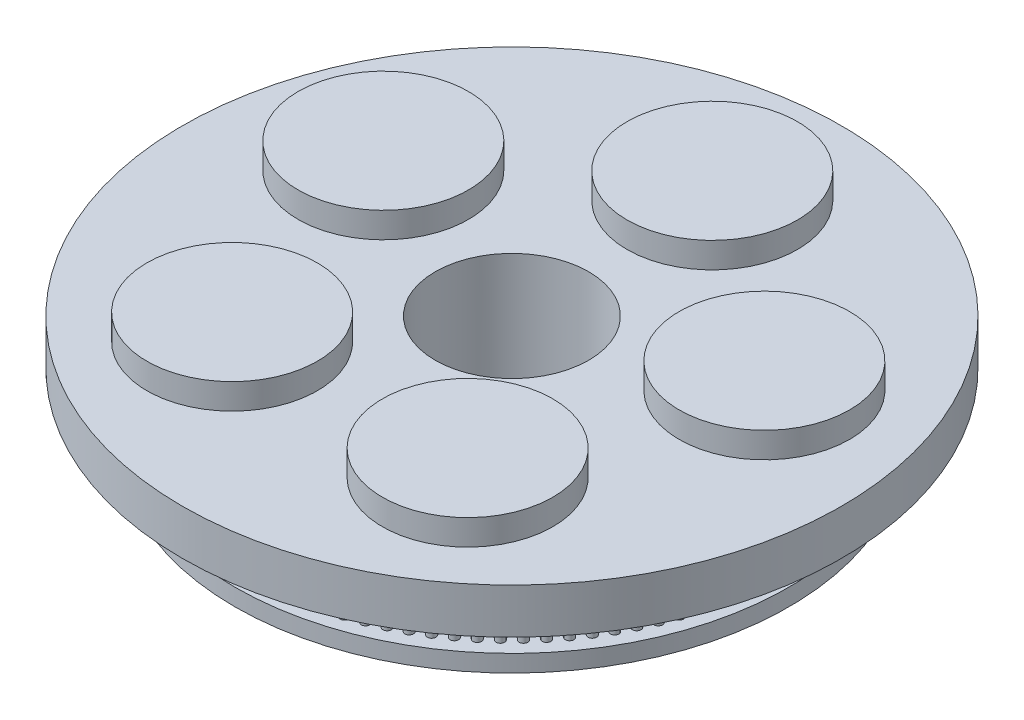
SolidWorks part; units mm, degrees
ref_plane "前基準面" through (0, 0, 0) normal (0, 0, 1) x (1, 0, 0)
ref_plane "上基準面" through (0, 0, 0) normal (0, 1, 0) x (1, 0, 0)
ref_plane "右基準面" through (0, 0, 0) normal (1, 0, 0) x (0, 0, -1)
sketch "草圖1" plane through (0, 0, 0) normal (0, 1, 0) x (1, 0, 0)
  circle A0 centre (0, 0) radius 38.66
  circle A1 centre (0, 0) radius 9
  dimension "D1" = 77.32
  dimension "D2" = 18
extrude "填料-伸長1" add sketch "草圖1" along normal blind 5.3
sketch "草圖3" plane through (0, 0, 0) normal (0, 0, 1) x (1, 0, 0)
  line L0 (0, 0) -> (0, 14.4931) construction
sketch "草圖2" plane through (0, 5.3, 0) normal (0, 1, 0) x (1, 0, 0)
  circle A0 centre (0, 23.5) radius 10
  dimension "D1" = 20
  dimension "D2" = 23.5
extrude "填料-伸長2" add sketch "草圖2" along normal blind 3
pattern_circular "環狀複製排列1" count 5 over 360 about axis through (0, 0, 0) along (0, 1, 0) of "填料-伸長2" reverse direction yes
sketch "草圖4" plane through (0, 0, 0) normal (0, -1, 0) x (1, 0, 0)
  line L0 (0, 0) -> (0, 38.66) construction
  line L1 (-0.5, 30.56) -> (-0.5, 29.9958) construction
  line L2 (-0.5, 30.56) -> (-0.5, 30.41)
  line L3 (0.5, 30.56) -> (0.5, 30.41)
  line L4 (1.4199, 30.5311) -> (1.4104, 30.3814)
  line L5 (2.4179, 30.4683) -> (2.4085, 30.3186)
  line L6 (3.3341, 30.3817) -> (3.3153, 30.2329)
  line L7 (4.3262, 30.2564) -> (4.3074, 30.1075)
  line L8 (5.2352, 30.1124) -> (5.2071, 29.965)
  line L9 (6.2175, 29.925) -> (6.1894, 29.7777)
  line L10 (7.1157, 29.7242) -> (7.0784, 29.579)
  line L11 (8.0843, 29.4756) -> (8.047, 29.3303)
  line L12 (8.968, 29.2188) -> (8.9217, 29.0761)
  line L13 (9.9191, 28.9098) -> (9.8727, 28.7671)
  line L14 (10.785, 28.598) -> (10.7298, 28.4586)
  line L15 (11.7148, 28.2299) -> (11.6596, 28.0904)
  line L16 (12.5594, 27.8644) -> (12.4955, 27.7287)
  line L17 (13.4642, 27.4386) -> (13.4004, 27.3029)
  line L18 (14.2842, 27.0208) -> (14.212, 26.8894)
  line L19 (15.1605, 26.5391) -> (15.0883, 26.4076)
  line L20 (15.9527, 26.0706) -> (15.8723, 25.9439)
  line L21 (16.797, 25.5347) -> (16.7167, 25.4081)
  line L22 (17.5582, 25.0175) -> (17.47, 24.8961)
  line L23 (18.3672, 24.4297) -> (18.2791, 24.3083)
  line L24 (19.0944, 23.8656) -> (18.9988, 23.75)
  line L25 (19.8649, 23.2282) -> (19.7693, 23.1126)
  line L26 (20.5553, 22.6196) -> (20.4526, 22.5102)
  line L27 (21.2842, 21.935) -> (21.1816, 21.8257)
  line L28 (21.935, 21.2842) -> (21.8257, 21.1816)
  line L29 (22.6196, 20.5553) -> (22.5102, 20.4526)
  line L30 (23.2282, 19.8649) -> (23.1126, 19.7693)
  line L31 (23.8656, 19.0944) -> (23.75, 18.9988)
  line L32 (24.4297, 18.3672) -> (24.3083, 18.2791)
  line L33 (25.0175, 17.5582) -> (24.8961, 17.47)
  line L34 (25.5347, 16.797) -> (25.4081, 16.7167)
  line L35 (26.0706, 15.9527) -> (25.9439, 15.8723)
  line L36 (26.5391, 15.1605) -> (26.4076, 15.0883)
  line L37 (27.0208, 14.2842) -> (26.8894, 14.212)
  line L38 (27.4386, 13.4642) -> (27.3029, 13.4004)
  line L39 (27.8644, 12.5594) -> (27.7287, 12.4955)
  line L40 (28.2299, 11.7148) -> (28.0904, 11.6596)
  line L41 (28.598, 10.785) -> (28.4586, 10.7298)
  line L42 (28.9098, 9.9191) -> (28.7671, 9.8727)
  line L43 (29.2188, 8.968) -> (29.0761, 8.9217)
  line L44 (29.4756, 8.0843) -> (29.3303, 8.047)
  line L45 (29.7242, 7.1157) -> (29.579, 7.0784)
  line L46 (29.925, 6.2175) -> (29.7777, 6.1894)
  line L47 (30.1124, 5.2352) -> (29.965, 5.2071)
  line L48 (30.2564, 4.3262) -> (30.1075, 4.3074)
  line L49 (30.3817, 3.3341) -> (30.2329, 3.3153)
  line L50 (30.4683, 2.4179) -> (30.3186, 2.4085)
  line L51 (30.5311, 1.4199) -> (30.3814, 1.4104)
  line L52 (30.56, 0.5) -> (30.41, 0.5)
  line L53 (30.56, -0.5) -> (30.41, -0.5)
  line L54 (30.5311, -1.4199) -> (30.3814, -1.4104)
  line L55 (30.4683, -2.4179) -> (30.3186, -2.4085)
  line L56 (30.3817, -3.3341) -> (30.2329, -3.3153)
  line L57 (30.2564, -4.3262) -> (30.1075, -4.3074)
  line L58 (30.1124, -5.2352) -> (29.965, -5.2071)
  line L59 (29.925, -6.2175) -> (29.7777, -6.1894)
  line L60 (29.7242, -7.1157) -> (29.579, -7.0784)
  line L61 (29.4756, -8.0843) -> (29.3303, -8.047)
  line L62 (29.2188, -8.968) -> (29.0761, -8.9217)
  line L63 (28.9098, -9.9191) -> (28.7671, -9.8727)
  line L64 (28.598, -10.785) -> (28.4586, -10.7298)
  line L65 (28.2299, -11.7148) -> (28.0904, -11.6596)
  line L66 (27.8644, -12.5594) -> (27.7287, -12.4955)
  line L67 (27.4386, -13.4642) -> (27.3029, -13.4004)
  line L68 (27.0208, -14.2842) -> (26.8894, -14.212)
  line L69 (26.5391, -15.1605) -> (26.4076, -15.0883)
  line L70 (26.0706, -15.9527) -> (25.9439, -15.8723)
  line L71 (25.5347, -16.797) -> (25.4081, -16.7167)
  line L72 (25.0175, -17.5582) -> (24.8961, -17.47)
  line L73 (24.4297, -18.3672) -> (24.3083, -18.2791)
  line L74 (23.8656, -19.0944) -> (23.75, -18.9988)
  line L75 (23.2282, -19.8649) -> (23.1126, -19.7693)
  line L76 (22.6196, -20.5553) -> (22.5102, -20.4526)
  line L77 (21.935, -21.2842) -> (21.8257, -21.1816)
  line L78 (21.2842, -21.935) -> (21.1816, -21.8257)
  line L79 (20.5553, -22.6196) -> (20.4526, -22.5102)
  line L80 (19.8649, -23.2282) -> (19.7693, -23.1126)
  line L81 (19.0944, -23.8656) -> (18.9988, -23.75)
  line L82 (18.3672, -24.4297) -> (18.2791, -24.3083)
  line L83 (17.5582, -25.0175) -> (17.47, -24.8961)
  line L84 (16.797, -25.5347) -> (16.7167, -25.4081)
  line L85 (15.9527, -26.0706) -> (15.8723, -25.9439)
  line L86 (15.1605, -26.5391) -> (15.0883, -26.4076)
  line L87 (14.2842, -27.0208) -> (14.212, -26.8894)
  line L88 (13.4642, -27.4386) -> (13.4004, -27.3029)
  line L89 (12.5594, -27.8644) -> (12.4955, -27.7287)
  line L90 (11.7148, -28.2299) -> (11.6596, -28.0904)
  line L91 (10.785, -28.598) -> (10.7298, -28.4586)
  line L92 (9.9191, -28.9098) -> (9.8727, -28.7671)
  line L93 (8.968, -29.2188) -> (8.9217, -29.0761)
  line L94 (8.0843, -29.4756) -> (8.047, -29.3303)
  line L95 (7.1157, -29.7242) -> (7.0784, -29.579)
  line L96 (6.2175, -29.925) -> (6.1894, -29.7777)
  line L97 (5.2352, -30.1124) -> (5.2071, -29.965)
  line L98 (4.3262, -30.2564) -> (4.3074, -30.1075)
  line L99 (3.3341, -30.3817) -> (3.3153, -30.2329)
  line L100 (2.4179, -30.4683) -> (2.4085, -30.3186)
  line L101 (1.4199, -30.5311) -> (1.4104, -30.3814)
  line L102 (0.5, -30.56) -> (0.5, -30.41)
  line L103 (-0.5, -30.56) -> (-0.5, -30.41)
  line L104 (-1.4199, -30.5311) -> (-1.4104, -30.3814)
  line L105 (-2.4179, -30.4683) -> (-2.4085, -30.3186)
  line L106 (-3.3341, -30.3817) -> (-3.3153, -30.2329)
  line L107 (-4.3262, -30.2564) -> (-4.3074, -30.1075)
  line L108 (-5.2352, -30.1124) -> (-5.2071, -29.965)
  line L109 (-6.2175, -29.925) -> (-6.1894, -29.7777)
  line L110 (-7.1157, -29.7242) -> (-7.0784, -29.579)
  line L111 (-8.0843, -29.4756) -> (-8.047, -29.3303)
  line L112 (-8.968, -29.2188) -> (-8.9217, -29.0761)
  line L113 (-9.9191, -28.9098) -> (-9.8727, -28.7671)
  line L114 (-10.785, -28.598) -> (-10.7298, -28.4586)
  line L115 (-11.7148, -28.2299) -> (-11.6596, -28.0904)
  line L116 (-12.5594, -27.8644) -> (-12.4955, -27.7287)
  line L117 (-13.4642, -27.4386) -> (-13.4004, -27.3029)
  line L118 (-14.2842, -27.0208) -> (-14.212, -26.8894)
  line L119 (-15.1605, -26.5391) -> (-15.0883, -26.4076)
  line L120 (-15.9527, -26.0706) -> (-15.8723, -25.9439)
  line L121 (-16.797, -25.5347) -> (-16.7167, -25.4081)
  line L122 (-17.5582, -25.0175) -> (-17.47, -24.8961)
  line L123 (-18.3672, -24.4297) -> (-18.2791, -24.3083)
  line L124 (-19.0944, -23.8656) -> (-18.9988, -23.75)
  line L125 (-19.8649, -23.2282) -> (-19.7693, -23.1126)
  line L126 (-20.5553, -22.6196) -> (-20.4526, -22.5102)
  line L127 (-21.2842, -21.935) -> (-21.1816, -21.8257)
  line L128 (-21.935, -21.2842) -> (-21.8257, -21.1816)
  line L129 (-22.6196, -20.5553) -> (-22.5102, -20.4526)
  line L130 (-23.2282, -19.8649) -> (-23.1126, -19.7693)
  line L131 (-23.8656, -19.0944) -> (-23.75, -18.9988)
  line L132 (-24.4297, -18.3672) -> (-24.3083, -18.2791)
  line L133 (-25.0175, -17.5582) -> (-24.8961, -17.47)
  line L134 (-25.5347, -16.797) -> (-25.4081, -16.7167)
  line L135 (-26.0706, -15.9527) -> (-25.9439, -15.8723)
  line L136 (-26.5391, -15.1605) -> (-26.4076, -15.0883)
  line L137 (-27.0208, -14.2842) -> (-26.8894, -14.212)
  line L138 (-27.4386, -13.4642) -> (-27.3029, -13.4004)
  line L139 (-27.8644, -12.5594) -> (-27.7287, -12.4955)
  line L140 (-28.2299, -11.7148) -> (-28.0904, -11.6596)
  line L141 (-28.598, -10.785) -> (-28.4586, -10.7298)
  line L142 (-28.9098, -9.9191) -> (-28.7671, -9.8727)
  line L143 (-29.2188, -8.968) -> (-29.0761, -8.9217)
  line L144 (-29.4756, -8.0843) -> (-29.3303, -8.047)
  line L145 (-29.7242, -7.1157) -> (-29.579, -7.0784)
  line L146 (-29.925, -6.2175) -> (-29.7777, -6.1894)
  line L147 (-30.1124, -5.2352) -> (-29.965, -5.2071)
  line L148 (-30.2564, -4.3262) -> (-30.1075, -4.3074)
  line L149 (-30.3817, -3.3341) -> (-30.2329, -3.3153)
  line L150 (-30.4683, -2.4179) -> (-30.3186, -2.4085)
  line L151 (-30.5311, -1.4199) -> (-30.3814, -1.4104)
  line L152 (-30.56, -0.5) -> (-30.41, -0.5)
  line L153 (-30.56, 0.5) -> (-30.41, 0.5)
  line L154 (-30.5311, 1.4199) -> (-30.3814, 1.4104)
  line L155 (-30.4683, 2.4179) -> (-30.3186, 2.4085)
  line L156 (-30.3817, 3.3341) -> (-30.2329, 3.3153)
  line L157 (-30.2564, 4.3262) -> (-30.1075, 4.3074)
  line L158 (-30.1124, 5.2352) -> (-29.965, 5.2071)
  line L159 (-29.925, 6.2175) -> (-29.7777, 6.1894)
  line L160 (-29.7242, 7.1157) -> (-29.579, 7.0784)
  line L161 (-29.4756, 8.0843) -> (-29.3303, 8.047)
  line L162 (-29.2188, 8.968) -> (-29.0761, 8.9217)
  line L163 (-28.9098, 9.9191) -> (-28.7671, 9.8727)
  line L164 (-28.598, 10.785) -> (-28.4586, 10.7298)
  line L165 (-28.2299, 11.7148) -> (-28.0904, 11.6596)
  line L166 (-27.8644, 12.5594) -> (-27.7287, 12.4955)
  line L167 (-27.4386, 13.4642) -> (-27.3029, 13.4004)
  line L168 (-27.0208, 14.2842) -> (-26.8894, 14.212)
  line L169 (-26.5391, 15.1605) -> (-26.4076, 15.0883)
  line L170 (-26.0706, 15.9527) -> (-25.9439, 15.8723)
  line L171 (-25.5347, 16.797) -> (-25.4081, 16.7167)
  line L172 (-25.0175, 17.5582) -> (-24.8961, 17.47)
  line L173 (-24.4297, 18.3672) -> (-24.3083, 18.2791)
  line L174 (-23.8656, 19.0944) -> (-23.75, 18.9988)
  line L175 (-23.2282, 19.8649) -> (-23.1126, 19.7693)
  line L176 (-22.6196, 20.5553) -> (-22.5102, 20.4526)
  line L177 (-21.935, 21.2842) -> (-21.8257, 21.1816)
  line L178 (-21.2842, 21.935) -> (-21.1816, 21.8257)
  line L179 (-20.5553, 22.6196) -> (-20.4526, 22.5102)
  line L180 (-19.8649, 23.2282) -> (-19.7693, 23.1126)
  line L181 (-19.0944, 23.8656) -> (-18.9988, 23.75)
  line L182 (-18.3672, 24.4297) -> (-18.2791, 24.3083)
  line L183 (-17.5582, 25.0175) -> (-17.47, 24.8961)
  line L184 (-16.797, 25.5347) -> (-16.7167, 25.4081)
  line L185 (-15.9527, 26.0706) -> (-15.8723, 25.9439)
  line L186 (-15.1605, 26.5391) -> (-15.0883, 26.4076)
  line L187 (-14.2842, 27.0208) -> (-14.212, 26.8894)
  line L188 (-13.4642, 27.4386) -> (-13.4004, 27.3029)
  line L189 (-12.5594, 27.8644) -> (-12.4955, 27.7287)
  line L190 (-11.7148, 28.2299) -> (-11.6596, 28.0904)
  line L191 (-10.785, 28.598) -> (-10.7298, 28.4586)
  line L192 (-9.9191, 28.9098) -> (-9.8727, 28.7671)
  line L193 (-8.968, 29.2188) -> (-8.9217, 29.0761)
  line L194 (-8.0843, 29.4756) -> (-8.047, 29.3303)
  line L195 (-7.1157, 29.7242) -> (-7.0784, 29.579)
  line L196 (-6.2175, 29.925) -> (-6.1894, 29.7777)
  line L197 (-5.2352, 30.1124) -> (-5.2071, 29.965)
  line L198 (-4.3262, 30.2564) -> (-4.3074, 30.1075)
  line L199 (-3.3341, 30.3817) -> (-3.3153, 30.2329)
  line L200 (-2.4179, 30.4683) -> (-2.4085, 30.3186)
  line L201 (-1.4199, 30.5311) -> (-1.4104, 30.3814)
  circle A0 centre (0, 0) radius 30.56 construction
  circle A1 centre (0, 0) radius 30
  circle A2 centre (0, 0) radius 38.66 construction
  arc A3 (0.5, 30.5559) -> (-0.5, 30.56) centre (0, 30.56) ccw
  arc A4 (-0.5, 30.41) -> (-0.9112, 29.9862) centre (-0.924, 30.41) cw
  arc A5 (2.4176, 30.4642) -> (1.4199, 30.5311) centre (1.9189, 30.4997) ccw
  arc A6 (1.4104, 30.3814) -> (0.9735, 29.9842) centre (0.9872, 30.408) cw
  arc A7 (0.5, 30.41) -> (0.9112, 29.9862) centre (0.924, 30.41) ccw
  arc A8 (2.4085, 30.3186) -> (2.7922, 29.8698) centre (2.8317, 30.292) ccw
  arc A9 (4.3257, 30.2523) -> (3.3341, 30.3817) centre (3.8302, 30.319) ccw
  arc A10 (3.3153, 30.2329) -> (2.8543, 29.8639) centre (2.8946, 30.286) cw
  arc A11 (4.3074, 30.1075) -> (4.6622, 29.6355) centre (4.7281, 30.0544) ccw
  arc A12 (6.2167, 29.921) -> (5.2352, 30.1124) centre (5.7264, 30.0187) ccw
  arc A13 (5.2071, 29.965) -> (4.7238, 29.6258) centre (4.7906, 30.0445) cw
  arc A14 (6.1894, 29.7777) -> (6.5139, 29.2843) centre (6.6059, 29.6982) ccw
  arc A15 (8.0832, 29.4716) -> (7.1157, 29.7242) centre (7.6, 29.5999) ccw
  arc A16 (7.0784, 29.579) -> (6.5747, 29.2707) centre (6.6677, 29.6844) cw
  arc A17 (8.047, 29.3303) -> (8.3398, 28.8175) centre (8.4577, 29.2248) ccw
  arc A18 (9.9178, 28.9059) -> (8.968, 29.2188) centre (9.4436, 29.0643) ccw
  arc A19 (8.9217, 29.0761) -> (8.3997, 28.8001) centre (8.5184, 29.2072) cw
  arc A20 (9.8727, 28.7671) -> (10.1328, 28.237) centre (10.276, 28.6361) ccw
  arc A21 (11.7133, 28.2261) -> (10.785, 28.598) centre (11.2499, 28.414) ccw
  arc A22 (10.7298, 28.4586) -> (10.1915, 28.2158) centre (10.3355, 28.6147) cw
  arc A23 (11.6596, 28.0904) -> (11.8858, 27.545) centre (12.0538, 27.9343) ccw
  arc A24 (13.4625, 27.4349) -> (12.5594, 27.8644) centre (13.0118, 27.6515) ccw
  arc A25 (12.4955, 27.7287) -> (11.943, 27.5202) centre (12.1119, 27.9092) cw
  arc A26 (13.4004, 27.3029) -> (13.5919, 26.7443) centre (13.784, 27.1224) ccw
  arc A27 (15.1586, 26.5355) -> (14.2842, 27.0208) centre (14.7224, 26.7799) ccw
  arc A28 (14.212, 26.8894) -> (13.6475, 26.716) centre (13.8404, 27.0936) cw
  arc A29 (15.0883, 26.4076) -> (15.2444, 25.8381) centre (15.4599, 26.2033) ccw
  arc A30 (16.7948, 25.5313) -> (15.9527, 26.0706) centre (16.3749, 25.8027) ccw
  arc A31 (15.8723, 25.9439) -> (15.2981, 25.8064) centre (15.5143, 26.1711) cw
  arc A32 (16.7167, 25.4081) -> (16.8367, 24.8299) centre (17.0747, 25.1809) ccw
  arc A33 (18.3648, 24.4264) -> (17.5582, 25.0175) centre (17.9627, 24.7236) ccw
  arc A34 (17.47, 24.8961) -> (16.8883, 24.7949) centre (17.127, 25.1453) cw
  arc A35 (18.2791, 24.3083) -> (18.3626, 23.7237) centre (18.6221, 24.0591) ccw
  arc A36 (19.8623, 23.225) -> (19.0944, 23.8656) centre (19.4797, 23.5469) ccw
  arc A37 (18.9988, 23.75) -> (18.4118, 23.6855) centre (18.6721, 24.0203) cw
  arc A38 (19.7693, 23.1126) -> (19.816, 22.5239) centre (20.096, 22.8423) ccw
  arc A39 (21.2814, 21.932) -> (20.5553, 22.6196) centre (20.9198, 22.2773) ccw
  arc A40 (20.4526, 22.5102) -> (19.8627, 22.4827) centre (20.1435, 22.8005) cw
  arc A41 (21.1816, 21.8257) -> (21.1911, 21.2352) centre (21.4907, 21.5354) ccw
  arc A42 (22.6166, 20.5525) -> (21.935, 21.2842) centre (22.2773, 20.9198) ccw
  arc A43 (21.8257, 21.1816) -> (21.2352, 21.1911) centre (21.5354, 21.4907) cw
  arc A44 (22.5102, 20.4526) -> (22.4827, 19.8627) centre (22.8005, 20.1435) ccw
  arc A45 (23.8624, 19.0918) -> (23.2282, 19.8649) centre (23.5469, 19.4797) ccw
  arc A46 (23.1126, 19.7693) -> (22.5239, 19.816) centre (22.8423, 20.096) cw
  arc A47 (23.75, 18.9988) -> (23.6855, 18.4118) centre (24.0203, 18.6721) ccw
  arc A48 (25.0141, 17.5558) -> (24.4297, 18.3672) centre (24.7236, 17.9627) ccw
  arc A49 (24.3083, 18.2791) -> (23.7237, 18.3626) centre (24.0591, 18.6221) cw
  arc A50 (24.8961, 17.47) -> (24.7949, 16.8883) centre (25.1453, 17.127) ccw
  arc A51 (26.0671, 15.9505) -> (25.5347, 16.797) centre (25.8027, 16.3749) ccw
  arc A52 (25.4081, 16.7167) -> (24.8299, 16.8367) centre (25.1809, 17.0747) cw
  arc A53 (25.9439, 15.8723) -> (25.8064, 15.2981) centre (26.1711, 15.5143) ccw
  arc A54 (27.0172, 14.2823) -> (26.5391, 15.1605) centre (26.7799, 14.7224) ccw
  arc A55 (26.4076, 15.0883) -> (25.8381, 15.2444) centre (26.2033, 15.4599) cw
  arc A56 (26.8894, 14.212) -> (26.716, 13.6475) centre (27.0936, 13.8404) ccw
  arc A57 (27.8607, 12.5577) -> (27.4386, 13.4642) centre (27.6515, 13.0118) ccw
  arc A58 (27.3029, 13.4004) -> (26.7443, 13.5919) centre (27.1224, 13.784) cw
  arc A59 (27.7287, 12.4955) -> (27.5202, 11.943) centre (27.9092, 12.1119) ccw
  arc A60 (28.5942, 10.7835) -> (28.2299, 11.7148) centre (28.414, 11.2499) ccw
  arc A61 (28.0904, 11.6596) -> (27.545, 11.8858) centre (27.9343, 12.0538) cw
  arc A62 (28.4586, 10.7298) -> (28.2158, 10.1915) centre (28.6147, 10.3355) ccw
  arc A63 (29.2149, 8.9668) -> (28.9098, 9.9191) centre (29.0643, 9.4436) ccw
  arc A64 (28.7671, 9.8727) -> (28.237, 10.1328) centre (28.6361, 10.276) cw
  arc A65 (29.0761, 8.9217) -> (28.8001, 8.3997) centre (29.2072, 8.5184) ccw
  arc A66 (29.7203, 7.1147) -> (29.4756, 8.0843) centre (29.5999, 7.6) ccw
  arc A67 (29.3303, 8.047) -> (28.8175, 8.3398) centre (29.2248, 8.4577) cw
  arc A68 (29.579, 7.0784) -> (29.2707, 6.5747) centre (29.6844, 6.6677) ccw
  arc A69 (30.1084, 5.2345) -> (29.925, 6.2175) centre (30.0187, 5.7264) ccw
  arc A70 (29.7777, 6.1894) -> (29.2843, 6.5139) centre (29.6982, 6.6059) cw
  arc A71 (29.965, 5.2071) -> (29.6258, 4.7238) centre (30.0445, 4.7906) ccw
  arc A72 (30.3776, 3.3336) -> (30.2564, 4.3262) centre (30.319, 3.8302) ccw
  arc A73 (30.1075, 4.3074) -> (29.6355, 4.6622) centre (30.0544, 4.7281) cw
  arc A74 (30.2329, 3.3153) -> (29.8639, 2.8543) centre (30.286, 2.8946) ccw
  arc A75 (30.527, 1.4196) -> (30.4683, 2.4179) centre (30.4997, 1.9189) ccw
  arc A76 (30.3186, 2.4085) -> (29.8698, 2.7922) centre (30.292, 2.8317) cw
  arc A77 (30.3814, 1.4104) -> (29.9842, 0.9735) centre (30.408, 0.9872) ccw
  arc A78 (30.5559, -0.5) -> (30.56, 0.5) centre (30.56, 0) ccw
  arc A79 (30.41, 0.5) -> (29.9862, 0.9112) centre (30.41, 0.924) cw
  arc A80 (30.41, -0.5) -> (29.9862, -0.9112) centre (30.41, -0.924) ccw
  arc A81 (30.4642, -2.4176) -> (30.5311, -1.4199) centre (30.4997, -1.9189) ccw
  arc A82 (30.3814, -1.4104) -> (29.9842, -0.9735) centre (30.408, -0.9872) cw
  arc A83 (30.3186, -2.4085) -> (29.8698, -2.7922) centre (30.292, -2.8317) ccw
  arc A84 (30.2523, -4.3257) -> (30.3817, -3.3341) centre (30.319, -3.8302) ccw
  arc A85 (30.2329, -3.3153) -> (29.8639, -2.8543) centre (30.286, -2.8946) cw
  arc A86 (30.1075, -4.3074) -> (29.6355, -4.6622) centre (30.0544, -4.7281) ccw
  arc A87 (29.921, -6.2167) -> (30.1124, -5.2352) centre (30.0187, -5.7264) ccw
  arc A88 (29.965, -5.2071) -> (29.6258, -4.7238) centre (30.0445, -4.7906) cw
  arc A89 (29.7777, -6.1894) -> (29.2843, -6.5139) centre (29.6982, -6.6059) ccw
  arc A90 (29.4716, -8.0832) -> (29.7242, -7.1157) centre (29.5999, -7.6) ccw
  arc A91 (29.579, -7.0784) -> (29.2707, -6.5747) centre (29.6844, -6.6677) cw
  arc A92 (29.3303, -8.047) -> (28.8175, -8.3398) centre (29.2248, -8.4577) ccw
  arc A93 (28.9059, -9.9178) -> (29.2188, -8.968) centre (29.0643, -9.4436) ccw
  arc A94 (29.0761, -8.9217) -> (28.8001, -8.3997) centre (29.2072, -8.5184) cw
  arc A95 (28.7671, -9.8727) -> (28.237, -10.1328) centre (28.6361, -10.276) ccw
  arc A96 (28.2261, -11.7133) -> (28.598, -10.785) centre (28.414, -11.2499) ccw
  arc A97 (28.4586, -10.7298) -> (28.2158, -10.1915) centre (28.6147, -10.3355) cw
  arc A98 (28.0904, -11.6596) -> (27.545, -11.8858) centre (27.9343, -12.0538) ccw
  arc A99 (27.4349, -13.4625) -> (27.8644, -12.5594) centre (27.6515, -13.0118) ccw
  arc A100 (27.7287, -12.4955) -> (27.5202, -11.943) centre (27.9092, -12.1119) cw
  arc A101 (27.3029, -13.4004) -> (26.7443, -13.5919) centre (27.1224, -13.784) ccw
  arc A102 (26.5355, -15.1586) -> (27.0208, -14.2842) centre (26.7799, -14.7224) ccw
  arc A103 (26.8894, -14.212) -> (26.716, -13.6475) centre (27.0936, -13.8404) cw
  arc A104 (26.4076, -15.0883) -> (25.8381, -15.2444) centre (26.2033, -15.4599) ccw
  arc A105 (25.5313, -16.7948) -> (26.0706, -15.9527) centre (25.8027, -16.3749) ccw
  arc A106 (25.9439, -15.8723) -> (25.8064, -15.2981) centre (26.1711, -15.5143) cw
  arc A107 (25.4081, -16.7167) -> (24.8299, -16.8367) centre (25.1809, -17.0747) ccw
  arc A108 (24.4264, -18.3648) -> (25.0175, -17.5582) centre (24.7236, -17.9627) ccw
  arc A109 (24.8961, -17.47) -> (24.7949, -16.8883) centre (25.1453, -17.127) cw
  arc A110 (24.3083, -18.2791) -> (23.7237, -18.3626) centre (24.0591, -18.6221) ccw
  arc A111 (23.225, -19.8623) -> (23.8656, -19.0944) centre (23.5469, -19.4797) ccw
  arc A112 (23.75, -18.9988) -> (23.6855, -18.4118) centre (24.0203, -18.6721) cw
  arc A113 (23.1126, -19.7693) -> (22.5239, -19.816) centre (22.8423, -20.096) ccw
  arc A114 (21.932, -21.2814) -> (22.6196, -20.5553) centre (22.2773, -20.9198) ccw
  arc A115 (22.5102, -20.4526) -> (22.4827, -19.8627) centre (22.8005, -20.1435) cw
  arc A116 (21.8257, -21.1816) -> (21.2352, -21.1911) centre (21.5354, -21.4907) ccw
  arc A117 (20.5525, -22.6166) -> (21.2842, -21.935) centre (20.9198, -22.2773) ccw
  arc A118 (21.1816, -21.8257) -> (21.1911, -21.2352) centre (21.4907, -21.5354) cw
  arc A119 (20.4526, -22.5102) -> (19.8627, -22.4827) centre (20.1435, -22.8005) ccw
  arc A120 (19.0918, -23.8624) -> (19.8649, -23.2282) centre (19.4797, -23.5469) ccw
  arc A121 (19.7693, -23.1126) -> (19.816, -22.5239) centre (20.096, -22.8423) cw
  arc A122 (18.9988, -23.75) -> (18.4118, -23.6855) centre (18.6721, -24.0203) ccw
  arc A123 (17.5558, -25.0141) -> (18.3672, -24.4297) centre (17.9627, -24.7236) ccw
  arc A124 (18.2791, -24.3083) -> (18.3626, -23.7237) centre (18.6221, -24.0591) cw
  arc A125 (17.47, -24.8961) -> (16.8883, -24.7949) centre (17.127, -25.1453) ccw
  arc A126 (15.9505, -26.0671) -> (16.797, -25.5347) centre (16.3749, -25.8027) ccw
  arc A127 (16.7167, -25.4081) -> (16.8367, -24.8299) centre (17.0747, -25.1809) cw
  arc A128 (15.8723, -25.9439) -> (15.2981, -25.8064) centre (15.5143, -26.1711) ccw
  arc A129 (14.2823, -27.0172) -> (15.1605, -26.5391) centre (14.7224, -26.7799) ccw
  arc A130 (15.0883, -26.4076) -> (15.2444, -25.8381) centre (15.4599, -26.2033) cw
  arc A131 (14.212, -26.8894) -> (13.6475, -26.716) centre (13.8404, -27.0936) ccw
  arc A132 (12.5577, -27.8607) -> (13.4642, -27.4386) centre (13.0118, -27.6515) ccw
  arc A133 (13.4004, -27.3029) -> (13.5919, -26.7443) centre (13.784, -27.1224) cw
  arc A134 (12.4955, -27.7287) -> (11.943, -27.5202) centre (12.1119, -27.9092) ccw
  arc A135 (10.7835, -28.5942) -> (11.7148, -28.2299) centre (11.2499, -28.414) ccw
  arc A136 (11.6596, -28.0904) -> (11.8858, -27.545) centre (12.0538, -27.9343) cw
  arc A137 (10.7298, -28.4586) -> (10.1915, -28.2158) centre (10.3355, -28.6147) ccw
  arc A138 (8.9668, -29.2149) -> (9.9191, -28.9098) centre (9.4436, -29.0643) ccw
  arc A139 (9.8727, -28.7671) -> (10.1328, -28.237) centre (10.276, -28.6361) cw
  arc A140 (8.9217, -29.0761) -> (8.3997, -28.8001) centre (8.5184, -29.2072) ccw
  arc A141 (7.1147, -29.7203) -> (8.0843, -29.4756) centre (7.6, -29.5999) ccw
  arc A142 (8.047, -29.3303) -> (8.3398, -28.8175) centre (8.4577, -29.2248) cw
  arc A143 (7.0784, -29.579) -> (6.5747, -29.2707) centre (6.6677, -29.6844) ccw
  arc A144 (5.2345, -30.1084) -> (6.2175, -29.925) centre (5.7264, -30.0187) ccw
  arc A145 (6.1894, -29.7777) -> (6.5139, -29.2843) centre (6.6059, -29.6982) cw
  arc A146 (5.2071, -29.965) -> (4.7238, -29.6258) centre (4.7906, -30.0445) ccw
  arc A147 (3.3336, -30.3776) -> (4.3262, -30.2564) centre (3.8302, -30.319) ccw
  arc A148 (4.3074, -30.1075) -> (4.6622, -29.6355) centre (4.7281, -30.0544) cw
  arc A149 (3.3153, -30.2329) -> (2.8543, -29.8639) centre (2.8946, -30.286) ccw
  arc A150 (1.4196, -30.527) -> (2.4179, -30.4683) centre (1.9189, -30.4997) ccw
  arc A151 (2.4085, -30.3186) -> (2.7922, -29.8698) centre (2.8317, -30.292) cw
  arc A152 (1.4104, -30.3814) -> (0.9735, -29.9842) centre (0.9872, -30.408) ccw
  arc A153 (-0.5, -30.5559) -> (0.5, -30.56) centre (0, -30.56) ccw
  arc A154 (0.5, -30.41) -> (0.9112, -29.9862) centre (0.924, -30.41) cw
  arc A155 (-0.5, -30.41) -> (-0.9112, -29.9862) centre (-0.924, -30.41) ccw
  arc A156 (-2.4176, -30.4642) -> (-1.4199, -30.5311) centre (-1.9189, -30.4997) ccw
  arc A157 (-1.4104, -30.3814) -> (-0.9735, -29.9842) centre (-0.9872, -30.408) cw
  arc A158 (-2.4085, -30.3186) -> (-2.7922, -29.8698) centre (-2.8317, -30.292) ccw
  arc A159 (-4.3257, -30.2523) -> (-3.3341, -30.3817) centre (-3.8302, -30.319) ccw
  arc A160 (-3.3153, -30.2329) -> (-2.8543, -29.8639) centre (-2.8946, -30.286) cw
  arc A161 (-4.3074, -30.1075) -> (-4.6622, -29.6355) centre (-4.7281, -30.0544) ccw
  arc A162 (-6.2167, -29.921) -> (-5.2352, -30.1124) centre (-5.7264, -30.0187) ccw
  arc A163 (-5.2071, -29.965) -> (-4.7238, -29.6258) centre (-4.7906, -30.0445) cw
  arc A164 (-6.1894, -29.7777) -> (-6.5139, -29.2843) centre (-6.6059, -29.6982) ccw
  arc A165 (-8.0832, -29.4716) -> (-7.1157, -29.7242) centre (-7.6, -29.5999) ccw
  arc A166 (-7.0784, -29.579) -> (-6.5747, -29.2707) centre (-6.6677, -29.6844) cw
  arc A167 (-8.047, -29.3303) -> (-8.3398, -28.8175) centre (-8.4577, -29.2248) ccw
  arc A168 (-9.9178, -28.9059) -> (-8.968, -29.2188) centre (-9.4436, -29.0643) ccw
  arc A169 (-8.9217, -29.0761) -> (-8.3997, -28.8001) centre (-8.5184, -29.2072) cw
  arc A170 (-9.8727, -28.7671) -> (-10.1328, -28.237) centre (-10.276, -28.6361) ccw
  arc A171 (-11.7133, -28.2261) -> (-10.785, -28.598) centre (-11.2499, -28.414) ccw
  arc A172 (-10.7298, -28.4586) -> (-10.1915, -28.2158) centre (-10.3355, -28.6147) cw
  arc A173 (-11.6596, -28.0904) -> (-11.8858, -27.545) centre (-12.0538, -27.9343) ccw
  arc A174 (-13.4625, -27.4349) -> (-12.5594, -27.8644) centre (-13.0118, -27.6515) ccw
  arc A175 (-12.4955, -27.7287) -> (-11.943, -27.5202) centre (-12.1119, -27.9092) cw
  arc A176 (-13.4004, -27.3029) -> (-13.5919, -26.7443) centre (-13.784, -27.1224) ccw
  arc A177 (-15.1586, -26.5355) -> (-14.2842, -27.0208) centre (-14.7224, -26.7799) ccw
  arc A178 (-14.212, -26.8894) -> (-13.6475, -26.716) centre (-13.8404, -27.0936) cw
  arc A179 (-15.0883, -26.4076) -> (-15.2444, -25.8381) centre (-15.4599, -26.2033) ccw
  arc A180 (-16.7948, -25.5313) -> (-15.9527, -26.0706) centre (-16.3749, -25.8027) ccw
  arc A181 (-15.8723, -25.9439) -> (-15.2981, -25.8064) centre (-15.5143, -26.1711) cw
  arc A182 (-16.7167, -25.4081) -> (-16.8367, -24.8299) centre (-17.0747, -25.1809) ccw
  arc A183 (-18.3648, -24.4264) -> (-17.5582, -25.0175) centre (-17.9627, -24.7236) ccw
  arc A184 (-17.47, -24.8961) -> (-16.8883, -24.7949) centre (-17.127, -25.1453) cw
  arc A185 (-18.2791, -24.3083) -> (-18.3626, -23.7237) centre (-18.6221, -24.0591) ccw
  arc A186 (-19.8623, -23.225) -> (-19.0944, -23.8656) centre (-19.4797, -23.5469) ccw
  arc A187 (-18.9988, -23.75) -> (-18.4118, -23.6855) centre (-18.6721, -24.0203) cw
  arc A188 (-19.7693, -23.1126) -> (-19.816, -22.5239) centre (-20.096, -22.8423) ccw
  arc A189 (-21.2814, -21.932) -> (-20.5553, -22.6196) centre (-20.9198, -22.2773) ccw
  arc A190 (-20.4526, -22.5102) -> (-19.8627, -22.4827) centre (-20.1435, -22.8005) cw
  arc A191 (-21.1816, -21.8257) -> (-21.1911, -21.2352) centre (-21.4907, -21.5354) ccw
  arc A192 (-22.6166, -20.5525) -> (-21.935, -21.2842) centre (-22.2773, -20.9198) ccw
  arc A193 (-21.8257, -21.1816) -> (-21.2352, -21.1911) centre (-21.5354, -21.4907) cw
  arc A194 (-22.5102, -20.4526) -> (-22.4827, -19.8627) centre (-22.8005, -20.1435) ccw
  arc A195 (-23.8624, -19.0918) -> (-23.2282, -19.8649) centre (-23.5469, -19.4797) ccw
  arc A196 (-23.1126, -19.7693) -> (-22.5239, -19.816) centre (-22.8423, -20.096) cw
  arc A197 (-23.75, -18.9988) -> (-23.6855, -18.4118) centre (-24.0203, -18.6721) ccw
  arc A198 (-25.0141, -17.5558) -> (-24.4297, -18.3672) centre (-24.7236, -17.9627) ccw
  arc A199 (-24.3083, -18.2791) -> (-23.7237, -18.3626) centre (-24.0591, -18.6221) cw
  arc A200 (-24.8961, -17.47) -> (-24.7949, -16.8883) centre (-25.1453, -17.127) ccw
  arc A201 (-26.0671, -15.9505) -> (-25.5347, -16.797) centre (-25.8027, -16.3749) ccw
  arc A202 (-25.4081, -16.7167) -> (-24.8299, -16.8367) centre (-25.1809, -17.0747) cw
  arc A203 (-25.9439, -15.8723) -> (-25.8064, -15.2981) centre (-26.1711, -15.5143) ccw
  arc A204 (-27.0172, -14.2823) -> (-26.5391, -15.1605) centre (-26.7799, -14.7224) ccw
  arc A205 (-26.4076, -15.0883) -> (-25.8381, -15.2444) centre (-26.2033, -15.4599) cw
  arc A206 (-26.8894, -14.212) -> (-26.716, -13.6475) centre (-27.0936, -13.8404) ccw
  arc A207 (-27.8607, -12.5577) -> (-27.4386, -13.4642) centre (-27.6515, -13.0118) ccw
  arc A208 (-27.3029, -13.4004) -> (-26.7443, -13.5919) centre (-27.1224, -13.784) cw
  arc A209 (-27.7287, -12.4955) -> (-27.5202, -11.943) centre (-27.9092, -12.1119) ccw
  arc A210 (-28.5942, -10.7835) -> (-28.2299, -11.7148) centre (-28.414, -11.2499) ccw
  arc A211 (-28.0904, -11.6596) -> (-27.545, -11.8858) centre (-27.9343, -12.0538) cw
  arc A212 (-28.4586, -10.7298) -> (-28.2158, -10.1915) centre (-28.6147, -10.3355) ccw
  arc A213 (-29.2149, -8.9668) -> (-28.9098, -9.9191) centre (-29.0643, -9.4436) ccw
  arc A214 (-28.7671, -9.8727) -> (-28.237, -10.1328) centre (-28.6361, -10.276) cw
  arc A215 (-29.0761, -8.9217) -> (-28.8001, -8.3997) centre (-29.2072, -8.5184) ccw
  arc A216 (-29.7203, -7.1147) -> (-29.4756, -8.0843) centre (-29.5999, -7.6) ccw
  arc A217 (-29.3303, -8.047) -> (-28.8175, -8.3398) centre (-29.2248, -8.4577) cw
  arc A218 (-29.579, -7.0784) -> (-29.2707, -6.5747) centre (-29.6844, -6.6677) ccw
  arc A219 (-30.1084, -5.2345) -> (-29.925, -6.2175) centre (-30.0187, -5.7264) ccw
  arc A220 (-29.7777, -6.1894) -> (-29.2843, -6.5139) centre (-29.6982, -6.6059) cw
  arc A221 (-29.965, -5.2071) -> (-29.6258, -4.7238) centre (-30.0445, -4.7906) ccw
  arc A222 (-30.3776, -3.3336) -> (-30.2564, -4.3262) centre (-30.319, -3.8302) ccw
  arc A223 (-30.1075, -4.3074) -> (-29.6355, -4.6622) centre (-30.0544, -4.7281) cw
  arc A224 (-30.2329, -3.3153) -> (-29.8639, -2.8543) centre (-30.286, -2.8946) ccw
  arc A225 (-30.527, -1.4196) -> (-30.4683, -2.4179) centre (-30.4997, -1.9189) ccw
  arc A226 (-30.3186, -2.4085) -> (-29.8698, -2.7922) centre (-30.292, -2.8317) cw
  arc A227 (-30.3814, -1.4104) -> (-29.9842, -0.9735) centre (-30.408, -0.9872) ccw
  arc A228 (-30.5559, 0.5) -> (-30.56, -0.5) centre (-30.56, 0) ccw
  arc A229 (-30.41, -0.5) -> (-29.9862, -0.9112) centre (-30.41, -0.924) cw
  arc A230 (-30.41, 0.5) -> (-29.9862, 0.9112) centre (-30.41, 0.924) ccw
  arc A231 (-30.4642, 2.4176) -> (-30.5311, 1.4199) centre (-30.4997, 1.9189) ccw
  arc A232 (-30.3814, 1.4104) -> (-29.9842, 0.9735) centre (-30.408, 0.9872) cw
  arc A233 (-30.3186, 2.4085) -> (-29.8698, 2.7922) centre (-30.292, 2.8317) ccw
  arc A234 (-30.2523, 4.3257) -> (-30.3817, 3.3341) centre (-30.319, 3.8302) ccw
  arc A235 (-30.2329, 3.3153) -> (-29.8639, 2.8543) centre (-30.286, 2.8946) cw
  arc A236 (-30.1075, 4.3074) -> (-29.6355, 4.6622) centre (-30.0544, 4.7281) ccw
  arc A237 (-29.921, 6.2167) -> (-30.1124, 5.2352) centre (-30.0187, 5.7264) ccw
  arc A238 (-29.965, 5.2071) -> (-29.6258, 4.7238) centre (-30.0445, 4.7906) cw
  arc A239 (-29.7777, 6.1894) -> (-29.2843, 6.5139) centre (-29.6982, 6.6059) ccw
  arc A240 (-29.4716, 8.0832) -> (-29.7242, 7.1157) centre (-29.5999, 7.6) ccw
  arc A241 (-29.579, 7.0784) -> (-29.2707, 6.5747) centre (-29.6844, 6.6677) cw
  arc A242 (-29.3303, 8.047) -> (-28.8175, 8.3398) centre (-29.2248, 8.4577) ccw
  arc A243 (-28.9059, 9.9178) -> (-29.2188, 8.968) centre (-29.0643, 9.4436) ccw
  arc A244 (-29.0761, 8.9217) -> (-28.8001, 8.3997) centre (-29.2072, 8.5184) cw
  arc A245 (-28.7671, 9.8727) -> (-28.237, 10.1328) centre (-28.6361, 10.276) ccw
  arc A246 (-28.2261, 11.7133) -> (-28.598, 10.785) centre (-28.414, 11.2499) ccw
  arc A247 (-28.4586, 10.7298) -> (-28.2158, 10.1915) centre (-28.6147, 10.3355) cw
  arc A248 (-28.0904, 11.6596) -> (-27.545, 11.8858) centre (-27.9343, 12.0538) ccw
  arc A249 (-27.4349, 13.4625) -> (-27.8644, 12.5594) centre (-27.6515, 13.0118) ccw
  arc A250 (-27.7287, 12.4955) -> (-27.5202, 11.943) centre (-27.9092, 12.1119) cw
  arc A251 (-27.3029, 13.4004) -> (-26.7443, 13.5919) centre (-27.1224, 13.784) ccw
  arc A252 (-26.5355, 15.1586) -> (-27.0208, 14.2842) centre (-26.7799, 14.7224) ccw
  arc A253 (-26.8894, 14.212) -> (-26.716, 13.6475) centre (-27.0936, 13.8404) cw
  arc A254 (-26.4076, 15.0883) -> (-25.8381, 15.2444) centre (-26.2033, 15.4599) ccw
  arc A255 (-25.5313, 16.7948) -> (-26.0706, 15.9527) centre (-25.8027, 16.3749) ccw
  arc A256 (-25.9439, 15.8723) -> (-25.8064, 15.2981) centre (-26.1711, 15.5143) cw
  arc A257 (-25.4081, 16.7167) -> (-24.8299, 16.8367) centre (-25.1809, 17.0747) ccw
  arc A258 (-24.4264, 18.3648) -> (-25.0175, 17.5582) centre (-24.7236, 17.9627) ccw
  arc A259 (-24.8961, 17.47) -> (-24.7949, 16.8883) centre (-25.1453, 17.127) cw
  arc A260 (-24.3083, 18.2791) -> (-23.7237, 18.3626) centre (-24.0591, 18.6221) ccw
  arc A261 (-23.225, 19.8623) -> (-23.8656, 19.0944) centre (-23.5469, 19.4797) ccw
  arc A262 (-23.75, 18.9988) -> (-23.6855, 18.4118) centre (-24.0203, 18.6721) cw
  arc A263 (-23.1126, 19.7693) -> (-22.5239, 19.816) centre (-22.8423, 20.096) ccw
  arc A264 (-21.932, 21.2814) -> (-22.6196, 20.5553) centre (-22.2773, 20.9198) ccw
  arc A265 (-22.5102, 20.4526) -> (-22.4827, 19.8627) centre (-22.8005, 20.1435) cw
  arc A266 (-21.8257, 21.1816) -> (-21.2352, 21.1911) centre (-21.5354, 21.4907) ccw
  arc A267 (-20.5525, 22.6166) -> (-21.2842, 21.935) centre (-20.9198, 22.2773) ccw
  arc A268 (-21.1816, 21.8257) -> (-21.1911, 21.2352) centre (-21.4907, 21.5354) cw
  arc A269 (-20.4526, 22.5102) -> (-19.8627, 22.4827) centre (-20.1435, 22.8005) ccw
  arc A270 (-19.0918, 23.8624) -> (-19.8649, 23.2282) centre (-19.4797, 23.5469) ccw
  arc A271 (-19.7693, 23.1126) -> (-19.816, 22.5239) centre (-20.096, 22.8423) cw
  arc A272 (-18.9988, 23.75) -> (-18.4118, 23.6855) centre (-18.6721, 24.0203) ccw
  arc A273 (-17.5558, 25.0141) -> (-18.3672, 24.4297) centre (-17.9627, 24.7236) ccw
  arc A274 (-18.2791, 24.3083) -> (-18.3626, 23.7237) centre (-18.6221, 24.0591) cw
  arc A275 (-17.47, 24.8961) -> (-16.8883, 24.7949) centre (-17.127, 25.1453) ccw
  arc A276 (-15.9505, 26.0671) -> (-16.797, 25.5347) centre (-16.3749, 25.8027) ccw
  arc A277 (-16.7167, 25.4081) -> (-16.8367, 24.8299) centre (-17.0747, 25.1809) cw
  arc A278 (-15.8723, 25.9439) -> (-15.2981, 25.8064) centre (-15.5143, 26.1711) ccw
  arc A279 (-14.2823, 27.0172) -> (-15.1605, 26.5391) centre (-14.7224, 26.7799) ccw
  arc A280 (-15.0883, 26.4076) -> (-15.2444, 25.8381) centre (-15.4599, 26.2033) cw
  arc A281 (-14.212, 26.8894) -> (-13.6475, 26.716) centre (-13.8404, 27.0936) ccw
  arc A282 (-12.5577, 27.8607) -> (-13.4642, 27.4386) centre (-13.0118, 27.6515) ccw
  arc A283 (-13.4004, 27.3029) -> (-13.5919, 26.7443) centre (-13.784, 27.1224) cw
  arc A284 (-12.4955, 27.7287) -> (-11.943, 27.5202) centre (-12.1119, 27.9092) ccw
  arc A285 (-10.7835, 28.5942) -> (-11.7148, 28.2299) centre (-11.2499, 28.414) ccw
  arc A286 (-11.6596, 28.0904) -> (-11.8858, 27.545) centre (-12.0538, 27.9343) cw
  arc A287 (-10.7298, 28.4586) -> (-10.1915, 28.2158) centre (-10.3355, 28.6147) ccw
  arc A288 (-8.9668, 29.2149) -> (-9.9191, 28.9098) centre (-9.4436, 29.0643) ccw
  arc A289 (-9.8727, 28.7671) -> (-10.1328, 28.237) centre (-10.276, 28.6361) cw
  arc A290 (-8.9217, 29.0761) -> (-8.3997, 28.8001) centre (-8.5184, 29.2072) ccw
  arc A291 (-7.1147, 29.7203) -> (-8.0843, 29.4756) centre (-7.6, 29.5999) ccw
  arc A292 (-8.047, 29.3303) -> (-8.3398, 28.8175) centre (-8.4577, 29.2248) cw
  arc A293 (-7.0784, 29.579) -> (-6.5747, 29.2707) centre (-6.6677, 29.6844) ccw
  arc A294 (-5.2345, 30.1084) -> (-6.2175, 29.925) centre (-5.7264, 30.0187) ccw
  arc A295 (-6.1894, 29.7777) -> (-6.5139, 29.2843) centre (-6.6059, 29.6982) cw
  arc A296 (-5.2071, 29.965) -> (-4.7238, 29.6258) centre (-4.7906, 30.0445) ccw
  arc A297 (-3.3336, 30.3776) -> (-4.3262, 30.2564) centre (-3.8302, 30.319) ccw
  arc A298 (-4.3074, 30.1075) -> (-4.6622, 29.6355) centre (-4.7281, 30.0544) cw
  arc A299 (-3.3153, 30.2329) -> (-2.8543, 29.8639) centre (-2.8946, 30.286) ccw
  arc A300 (-1.4196, 30.527) -> (-2.4179, 30.4683) centre (-1.9189, 30.4997) ccw
  arc A301 (-2.4085, 30.3186) -> (-2.7922, 29.8698) centre (-2.8317, 30.292) cw
  arc A302 (-1.4104, 30.3814) -> (-0.9735, 29.9842) centre (-0.9872, 30.408) ccw
  point P1011 (0, 0)
  dimension "D1" = 61.12
  dimension "D2" = 60
  dimension "D3" = 1
  dimension "D4" = 0.15
  dimension "D5" = 100
extrude "填料-伸長3" add sketch "草圖4" along normal blind 6 contours A1 | A293 L195 A291 L194 A292 A1 | A290 L193 A288 L192 A289 A1 | A287 L191 A285 L190 A286 A1 | A284 L189 A282 L188 A283 A1 | A296 L197 A294 L196 A295 A1 | A299 L199 A297 L198 A298 A1 | A302 L201 A300 L200 A301 A1 | A7 L3 A3 L2 A4 A1 | A8 L5 A5 L4 A6 A1 | A11 L7 A9 L6 A10 A1 | A14 L9 A12 L8 A13 A1 | A17 L11 A15 L10 A16 A1 | A20 L13 A18 L12 A19 A1 | A23 L15 A21 L14 A22 A1 | A26 L17 A24 L16 A25 A1 | A29 L19 A27 L18 A28 A1 | A32 L21 A30 L20 A31 A1 | A35 L23 A33 L22 A34 A1 | A38 L25 A36 L24 A37 A1 | A41 L27 A39 L26 A40 A1 | A44 L29 A42 L28 A43 A1 | A47 L31 A45 L30 A46 A1 | A50 L33 A48 L32 A49 A1 | A53 L35 A51 L34 A52 A1 | A56 L37 A54 L36 A55 A1 | A59 L39 A57 L38 A58 A1 | A62 L41 A60 L40 A61 A1 | A65 L43 A63 L42 A64 A1 | A68 L45 A66 L44 A67 A1 | A71 L47 A69 L46 A70 A1 | A74 L49 A72 L48 A73 A1 | A77 L51 A75 L50 A76 A1 | A80 L53 A78 L52 A79 A1 | A83 L55 A81 L54 A82 A1 | A86 L57 A84 L56 A85 A1 | A89 L59 A87 L58 A88 A1 | A92 L61 A90 L60 A91 A1 | A95 L63 A93 L62 A94 A1 | A98 L65 A96 L64 A97 A1 | A101 L67 A99 L66 A100 A1 | A104 L69 A102 L68 A103 A1 | A107 L71 A105 L70 A106 A1 | A110 L73 A108 L72 A109 A1 | A113 L75 A111 L74 A112 A1 | A116 L77 A114 L76 A115 A1 | A119 L79 A117 L78 A118 A1 | A122 L81 A120 L80 A121 A1 | A125 L83 A123 L82 A124 A1 | A128 L85 A126 L84 A127 A1 | A131 L87 A129 L86 A130 A1 | A134 L89 A132 L88 A133 A1 | A137 L91 A135 L90 A136 A1 | A140 L93 A138 L92 A139 A1 | A143 L95 A141 L94 A142 A1 | A146 L97 A144 L96 A145 A1 | A149 L99 A147 L98 A148 A1 | A152 L101 A150 L100 A151 A1 | A155 L103 A153 L102 A154 A1 | A158 L105 A156 L104 A157 A1 | A161 L107 A159 L106 A160 A1 | A164 L109 A162 L108 A163 A1 | A167 L111 A165 L110 A166 A1 | A170 L113 A168 L112 A169 A1 | A173 L115 A171 L114 A172 A1 | A176 L117 A174 L116 A175 A1 | A179 L119 A177 L118 A178 A1 | A182 L121 A180 L120 A181 A1 | A185 L123 A183 L122 A184 A1 | A188 L125 A186 L124 A187 A1 | A191 L127 A189 L126 A190 A1 | A194 L129 A192 L128 A193 A1 | A200 L133 A198 L132 A199 A1 | A203 L135 A201 L134 A202 A1 | A206 L137 A204 L136 A205 A1 | A209 L139 A207 L138 A208 A1 | A212 L141 A210 L140 A211 A1 | A197 L131 A195 L130 A196 A1 | A215 L143 A213 L142 A214 A1 | A218 L145 A216 L144 A217 A1 | A221 L147 A219 L146 A220 A1 | A224 L149 A222 L148 A223 A1 | A227 L151 A225 L150 A226 A1 | A230 L153 A228 L152 A229 A1 | A233 L155 A231 L154 A232 A1 | A236 L157 A234 L156 A235 A1 | A239 L159 A237 L158 A238 A1 | A242 L161 A240 L160 A241 A1 | A245 L163 A243 L162 A244 A1 | A248 L165 A246 L164 A247 A1 | A251 L167 A249 L166 A250 A1 | A254 L169 A252 L168 A253 A1 | A257 L171 A255 L170 A256 A1 | A260 L173 A258 L172 A259 A1 | A263 L175 A261 L174 A262 A1 | A266 L177 A264 L176 A265 A1 | A269 L179 A267 L178 A268 A1 | A272 L181 A270 L180 A271 A1 | A275 L183 A273 L182 A274 A1 | A278 L185 A276 L184 A277 A1 | A281 L187 A279 L186 A280 A1 | A1 region at (0, 0, 30.4542) region at (0, 0, 0) region at (-1.9122, 0, 30.3941) region at (1.9122, 0, 30.3941) region at (-3.8169, 0, 30.214) region at (3.8169, 0, 30.214) region at (-5.7065, 0, 29.9147) region at (5.7065, 0, 29.9147) region at (-7.5736, 0, 29.4974) region at (7.5736, 0, 29.4974) region at (-9.4109, 0, 28.9636) region at (9.4109, 0, 28.9636) region at (-11.2109, 0, 28.3156) region at (11.2109, 0, 28.3156) region at (-12.9668, 0, 27.5558) region at (12.9668, 0, 27.5558) region at (-14.6714, 0, 26.6872) region at (14.6714, 0, 26.6872) region at (-16.3182, 0, 25.7133) region at (16.3182, 0, 25.7133) region at (-17.9005, 0, 24.6379) region at (17.9005, 0, 24.6379) region at (-19.4122, 0, 23.4653) region at (19.4122, 0, 23.4653) region at (-20.8473, 0, 22.2001) region at (20.8473, 0, 22.2001) region at (-22.2001, 0, 20.8473) region at (22.2001, 0, 20.8473) region at (-23.4653, 0, 19.4122) region at (23.4653, 0, 19.4122) region at (-24.6379, 0, 17.9005) region at (24.6379, 0, 17.9005) region at (-25.7133, 0, 16.3182) region at (25.7133, 0, 16.3182) region at (-26.6872, 0, 14.6714) region at (26.6872, 0, 14.6714) region at (-27.5558, 0, 12.9668) region at (27.5558, 0, 12.9668) region at (-28.3156, 0, 11.2109) region at (28.3156, 0, 11.2109) region at (-28.9636, 0, 9.4109) region at (28.9636, 0, 9.4109) region at (-29.4974, 0, 7.5736) region at (29.4974, 0, 7.5736) region at (-29.9147, 0, 5.7065) region at (29.9147, 0, 5.7065) region at (-30.214, 0, 3.8169) region at (30.214, 0, 3.8169) region at (-30.3941, 0, 1.9122) region at (30.3941, 0, 1.9122) region at (-30.4542, 0, 0) region at (30.4542, 0, 0) region at (-30.3941, 0, -1.9122) region at (30.3941, 0, -1.9122) region at (-30.214, 0, -3.8169) region at (30.214, 0, -3.8169) region at (-29.9147, 0, -5.7065) region at (29.9147, 0, -5.7065) region at (-29.4974, 0, -7.5736) region at (29.4974, 0, -7.5736)
sketch "草圖5" plane through (0, -6, 0) normal (0, -1, 0) x (1, 0, 0)
  circle A0 centre (0, 0) radius 32.5
  dimension "D1" = 65
extrude "填料-伸長4" add sketch "草圖5" along normal blind 2
sketch "草圖6" plane through (0, -8, 0) normal (0, -1, 0) x (1, 0, 0)
  circle A0 centre (0, 0) radius 9
  dimension "D1" = 18
extrude "除料-伸長1" cut sketch "草圖6" against normal through all
